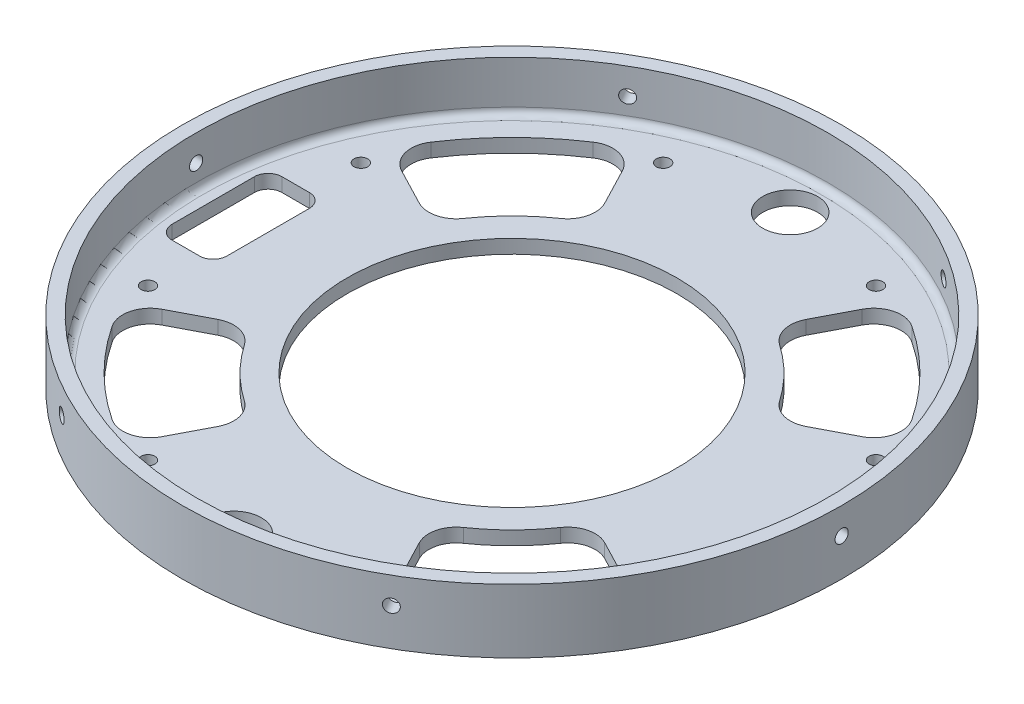
SolidWorks part; units mm, degrees
material "6061-T6 (SS)"
ref_plane "Front Plane" through (0, 0, 0) normal (0, 0, 1) x (1, 0, 0)
ref_plane "Top Plane" through (0, 0, 0) normal (0, 1, 0) x (1, 0, 0)
ref_plane "Right Plane" through (0, 0, 0) normal (1, 0, 0) x (0, 0, -1)
sketch "Sketch1" plane through (0, 0, 0) normal (0, 1, 0) x (1, 0, 0)
  circle A0 centre (0, 0) radius 76.2
extrude "Boss-Extrude1" add sketch "Sketch1" along normal blind 16.256
shell "Shell1" thickness 3.175 removed face at (0, 16.256, 76.2)
fillet "Fillet1" radius 1.5875 1 edges at (0, 3.175, 73.025)
sketch "Sketch2" plane through (0, 0, 0) normal (0, -1, 0) x (1, 0, 0)
  circle A0 centre (0, 0) radius 38.1
  dimension "D1" = 76.2
extrude "Cut-Extrude1" cut sketch "Sketch2" against normal blind 16.256
sketch "Sketch3" plane through (0, 0, 0) normal (1, 0, 0) x (0, 0, -1)
  line L0 (0, 0) -> (0, 8.636) construction
  circle A0 centre (0, 8.636) radius 1.524
  dimension "D2" = 3.048
  dimension "D1" = 8.636
extrude "Cut-Extrude2" cut sketch "Sketch3" against normal blind 76.2
pattern_circular "CirPattern1" count 6 over 360 about axis through (0, 16.256, 0) along (0, -1, 0) of "Cut-Extrude2"
sketch "Sketch5" plane through (0, 16.256, 0) normal (0, 1, 0) x (1, 0, 0)
  circle A0 centre (0, 0) radius 76.2
extrude "Cut-Extrude4" cut sketch "Sketch5" against normal blind 1.524
sketch "Sketch6" plane through (0, 3.175, 0) normal (0, 1, 0) x (1, 0, 0)
  line L0 (0, 0) -> (0, 71.4375) construction
  line L1 (0, 0) -> (61.8667, 35.7187) construction
  line L2 (0, 0) -> (61.8667, -35.7188) construction
  line L3 (0, 0) -> (0, -71.4375) construction
  line L4 (0, 0) -> (-61.8667, -35.7187) construction
  line L5 (0, 0) -> (-61.8667, 35.7188) construction
  circle A0 centre (0, 0) radius 71.4375 construction
  circle A1 centre (0, 0) radius 73.025 construction
  circle A2 centre (0, 64.2874) radius 6.35
  circle A3 centre (0, -64.2874) radius 6.35
  point P15 (0, 0)
  dimension "D2" = 64.2874
  dimension "D4" = 12.7
  dimension "D5" = 12.7
  dimension "D3" = 64.2874
  dimension "D1" = 6
extrude "Cut-Extrude5" cut sketch "Sketch6" against normal blind 12.7
sketch "Sketch7" plane through (0, 3.175, 0) normal (0, 1, 0) x (1, 0, 0)
  line L0 (0, 0) -> (0, 59.525) construction
  line L1 (24.6, 59.525) -> (-24.6, 59.525) construction
  line L2 (0, 0) -> (-76.2, 0) construction
  line L3 (24.6, -59.525) -> (-24.6, -59.525) construction
  line L4 (0, 0) -> (0, -59.525) construction
  line L5 (0, 0) -> (53.8815, 53.8815) construction
  line L6 (-59.525, 24.6) -> (-59.525, -24.6) construction
  line L7 (59.525, 24.6) -> (59.525, -24.6) construction
  line L8 (-59.525, 0) -> (59.525, 0) construction
  circle A0 centre (-24.6, 59.525) radius 1.5875
  circle A1 centre (24.6, 59.525) radius 1.5875
  circle A2 centre (0, 0) radius 76.2 construction
  circle A3 centre (24.6, -59.525) radius 1.5875
  circle A4 centre (-24.6, -59.525) radius 1.5875
  circle A5 centre (-59.525, -24.6) radius 1.5875
  circle A6 centre (-59.525, 24.6) radius 1.5875
  circle A7 centre (59.525, 24.6) radius 1.5875
  circle A8 centre (59.525, -24.6) radius 1.5875
  dimension "D1" = 3.175
  dimension "D2" = 24.6
  dimension "D3" = 59.525
extrude "Cut-Extrude6" cut sketch "Sketch7" against normal blind 6.35
sketch "Sketch8" plane through (0, 3.175, 0) normal (0, 1, 0) x (1, 0, 0)
  line L0 (0, 0) -> (-76.2, 0) construction
  line L2 (-69.05, -12.7) -> (-56.35, -12.7)
  line L3 (-69.05, -12.7) -> (-69.05, 12.7)
  line L4 (-69.05, 12.7) -> (-56.35, 12.7)
  line L5 (-56.35, -12.7) -> (-56.35, 12.7)
  line L6 (-69.05, -12.7) -> (-56.35, 12.7) construction
  line L7 (-69.05, 12.7) -> (-56.35, -12.7) construction
  circle A0 centre (0, 0) radius 76.2 construction
  point P6 (-62.7, 0)
  dimension "D1" = 69.05
  dimension "D2" = 12.7
  dimension "D3" = 25.4
extrude "Cut-Extrude7" cut sketch "Sketch8" against normal blind 6.35
fillet "Fillet2" radius 3.175 4 edges at (-69.05, 1.5875, 12.7) (-56.35, 1.5875, 12.7) (-56.35, 1.5875, -12.7) (-69.05, 1.5875, -12.7)
sketch "Sketch9" plane through (0, 3.175, 0) normal (0, 1, 0) x (1, 0, 0)
  line L0 (-76.2, 0) -> (76.2, 0) construction
  line L1 (0, 76.2) -> (0, -76.2) construction
  line L2 (-27.7002, 53.2117) -> (-23.2729, 44.7067)
  line L3 (0, 0) -> (-67.5902, 35.1852) construction
  line L4 (0, 0) -> (-35.1852, 67.5902) construction
  line L5 (-44.7067, 23.2729) -> (-53.2117, 27.7002)
  line L6 (44.7067, 23.2729) -> (53.2117, 27.7002)
  line L7 (27.7002, 53.2117) -> (23.2729, 44.7067)
  line L8 (27.7002, -53.2117) -> (23.2729, -44.7067)
  line L9 (44.7067, -23.2729) -> (53.2117, -27.7002)
  line L10 (-44.7067, -23.2729) -> (-53.2117, -27.7002)
  line L11 (-27.7002, -53.2117) -> (-23.2729, -44.7067)
  circle A0 centre (0, 0) radius 76.2 construction
  circle A1 centre (0, 0) radius 38.1 construction
  circle A2 centre (0, 0) radius 71.4375 construction
  arc A3 (-25.2922, 36.5528) -> (-36.5528, 25.2922) centre (0, 0) ccw
  arc A4 (-36.8415, 55.5721) -> (-55.5721, 36.8415) centre (0, 0) ccw
  circle A5 centre (0, 0) radius 73.025 construction
  arc A6 (-53.2117, 27.7002) -> (-55.5721, 36.8415) centre (-50.2796, 33.3328) cw
  arc A7 (-44.7067, 23.2729) -> (-36.5528, 25.2922) centre (-41.7746, 28.9054) ccw
  arc A8 (-23.2729, 44.7067) -> (-25.2922, 36.5528) centre (-28.9054, 41.7746) cw
  arc A9 (-27.7002, 53.2117) -> (-36.8415, 55.5721) centre (-33.3328, 50.2796) ccw
  arc A10 (27.7002, 53.2117) -> (36.8415, 55.5721) centre (33.3328, 50.2796) cw
  arc A11 (23.2729, 44.7067) -> (25.2922, 36.5528) centre (28.9054, 41.7746) ccw
  arc A12 (44.7067, 23.2729) -> (36.5528, 25.2922) centre (41.7746, 28.9054) cw
  arc A13 (53.2117, 27.7002) -> (55.5721, 36.8415) centre (50.2796, 33.3328) ccw
  arc A14 (36.8415, 55.5721) -> (55.5721, 36.8415) centre (0, 0) cw
  arc A15 (25.2922, 36.5528) -> (36.5528, 25.2922) centre (0, 0) cw
  arc A16 (25.2922, -36.5528) -> (36.5528, -25.2922) centre (0, 0) ccw
  arc A17 (36.8415, -55.5721) -> (55.5721, -36.8415) centre (0, 0) ccw
  arc A18 (53.2117, -27.7002) -> (55.5721, -36.8415) centre (50.2796, -33.3328) cw
  arc A19 (44.7067, -23.2729) -> (36.5528, -25.2922) centre (41.7746, -28.9054) ccw
  arc A20 (23.2729, -44.7067) -> (25.2922, -36.5528) centre (28.9054, -41.7746) cw
  arc A21 (27.7002, -53.2117) -> (36.8415, -55.5721) centre (33.3328, -50.2796) ccw
  arc A22 (-27.7002, -53.2117) -> (-36.8415, -55.5721) centre (-33.3328, -50.2796) cw
  arc A23 (-23.2729, -44.7067) -> (-25.2922, -36.5528) centre (-28.9054, -41.7746) ccw
  arc A24 (-44.7067, -23.2729) -> (-36.5528, -25.2922) centre (-41.7746, -28.9054) cw
  arc A25 (-53.2117, -27.7002) -> (-55.5721, -36.8415) centre (-50.2796, -33.3328) ccw
  arc A26 (-36.8415, -55.5721) -> (-55.5721, -36.8415) centre (0, 0) cw
  arc A27 (-25.2922, -36.5528) -> (-36.5528, -25.2922) centre (0, 0) cw
  point P21 (-59.1414, 30.7871)
  point P24 (-39.4276, 20.5247)
  point P41 (39.4276, 20.5247)
  point P42 (59.1414, 30.7871)
  point P55 (59.1414, -30.7871)
  point P56 (39.4276, -20.5247)
  point P69 (-39.4276, -20.5247)
  point P70 (-59.1414, -30.7871)
  dimension "D3" = 76.2
  dimension "D4" = 142.875
  dimension "D5" = 6.35
  dimension "D6" = 6.35
  dimension "D8" = 6.35
  dimension "D1" = 27.5
  dimension "D2" = 27.5
  dimension "D7" = 27.5
extrude "Cut-Extrude8" cut sketch "Sketch9" against normal blind 6.35
